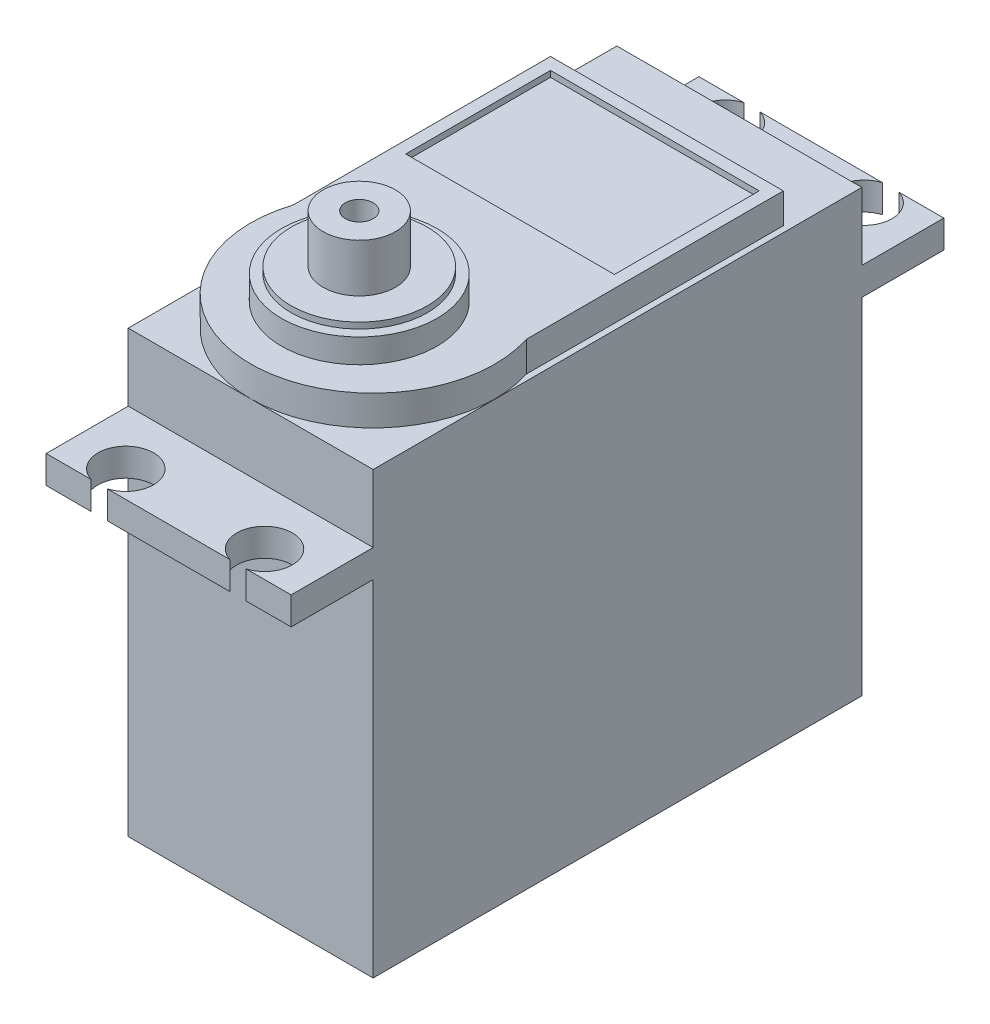
SolidWorks part; units mm, degrees
ref_plane "Front Plane" through (0, 0, 0) normal (0, 0, 1) x (1, 0, 0)
ref_plane "Top Plane" through (0, 0, 0) normal (0, 1, 0) x (1, 0, 0)
ref_plane "Right Plane" through (0, 0, 0) normal (1, 0, 0) x (0, 0, -1)
sketch "Sketch1" plane through (0, 0, 0) normal (0, 1, 0) x (1, 0, 0)
  line L1 (-10.15, -20.25) -> (10.15, -20.25)
  line L2 (-10.15, -20.25) -> (-10.15, 20.25)
  line L3 (-10.15, 20.25) -> (10.15, 20.25)
  line L4 (10.15, -20.25) -> (10.15, 20.25)
  line L5 (-10.15, -20.25) -> (10.15, 20.25) construction
  line L6 (-10.15, 20.25) -> (10.15, -20.25) construction
  point P0 (0, 0)
  dimension "D1" = 40.5
  dimension "D2" = 20.3
extrude "Boss-Extrude1" add sketch "Sketch1" along normal blind 36.5
sketch "Sketch4" plane through (0, 0, 20.25) normal (0, 0, 1) x (1, 0, 0)
  line L0 (10.15, 0) -> (10.15, 28.6) construction
  line L1 (10.15, 36.5) -> (10.15, 0) construction
  line L2 (10.15, 28.6) -> (-10.15, 28.6)
  line L3 (-10.15, 36.5) -> (-10.15, 0) construction
  line L4 (-10.15, 28.6) -> (-10.15, 30.9)
  line L5 (-10.15, 30.9) -> (10.15, 30.9)
  line L6 (10.15, 30.9) -> (10.15, 28.6)
  dimension "D1" = 28.6
  dimension "D2" = 2.3
extrude "Boss-Extrude4" add sketch "Sketch4" along normal blind 6.8 contours L5 L6 L2 L4
sketch "Sketch5" plane through (0, 30.9, 0) normal (0, 1, 0) x (1, 0, 0)
  line L0 (0, -20.25) -> (0, -22.35) construction
  line L1 (-10.15, -20.25) -> (10.15, -20.25) construction
  line L2 (-10.15, -22.35) -> (10.15, -22.35) construction
  line L3 (10.15, -27.05) -> (10.15, -20.25) construction
  line L4 (0, -22.35) -> (0, -27.05) construction
  line L5 (-10.15, -27.05) -> (10.15, -27.05) construction
  line L7 (10.15, -27.05) -> (8.05, -27.05) construction
  line L8 (8.05, -27.05) -> (5.75, -27.05)
  line L9 (5.75, -27.05) -> (5.75, -24.85)
  circle A0 centre (5.75, -24.85) radius 2.3
  circle A1 centre (-5.75, -24.85) radius 2.3
  point P10 (0, -22.35)
  line M10 (-10.15, -27.05) -> (10.15, -27.05)
  dimension "D2" = 4.6
  dimension "D1" = 2.1
  dimension "D3" = 2.1
  dimension "D4" = 2.2
  dimension "D5" = 2.3
extrude "Cut-Extrude1" cut sketch "Sketch5" against normal up to body separate body contours A1 M10 | A0 M10 region at (-5.75, 30.9, 24.8378) region at (5.75, 30.9, 24.8378)
sketch "Sketch6" plane through (-10.15, 0, 0) normal (-1, 0, 0) x (0, 0, 1)
  line L0 (0, 0) -> (0, 36.5) construction
  line L1 (-20.25, 0) -> (20.25, 0) construction
  line L2 (-20.25, 36.5) -> (20.25, 36.5) construction
ref_plane "Plane1" through (0, 0, 0) normal (0, 0, 1) x (0, 1, 0)
mirror "Mirror2" about plane through (0, 0, 0) normal (0, 0, 1) of "Cut-Extrude1", "Boss-Extrude4"
sketch "Sketch7" plane through (0, 36.5, 0) normal (0, 1, 0) x (1, 0, 0)
  line L0 (10.15, 20.25) -> (-10.15, 20.25) construction
  line L1 (10.15, -20.25) -> (10.15, 20.25) construction
  line L2 (10.15, 14.75) -> (-10.15, 14.75)
  line L3 (-10.15, 20.25) -> (-10.15, -20.25) construction
  line L4 (-10.15, 14.75) -> (-10.15, -7.05)
  line L5 (10.15, 14.75) -> (10.15, -7.05) construction
  line L6 (0, -20.25) -> (0, 11.25) construction
  line L7 (-10.15, -20.25) -> (10.15, -20.25) construction
  line L8 (-9.65, 14.25) -> (-9.65, -7.05)
  line L9 (9.65, 14.25) -> (-9.65, 14.25)
  line L10 (9.65, 14.25) -> (9.65, -7.05)
  arc A0 (9.65, -7.05) -> (-9.65, -7.05) centre (0, -10.1226) cw
  dimension "D1" = 5.5
  dimension "D2" = 13.2
  dimension "D3" = 31.5
  dimension "D4" = 0.5
extrude "Boss-Extrude5" add sketch "Sketch7" along normal blind 2.5 contours A0 L8 L9 L10
sketch "Sketch10" plane through (0, 39, 0) normal (0, 1, 0) x (1, 0, 0)
  line L0 (0, -20.25) -> (0, -11.25) construction
  arc A0 (-9.65, -7.05) -> (9.65, -7.05) centre (0, -10.1226) ccw construction
  circle A1 centre (0, -11.25) radius 6.45
  dimension "D2" = 12.9
  dimension "D1" = 9
extrude "Boss-Extrude6" add sketch "Sketch10" along normal blind 2
sketch "Sketch11" plane through (0, 41, 0) normal (0, 1, 0) x (1, 0, 0)
  circle A0 centre (0, -11.25) radius 6.45 construction
  circle A1 centre (0, -11.25) radius 5.65
  dimension "D1" = 0.8
extrude "Boss-Extrude7" add sketch "Sketch11" along normal blind 0.5
sketch "Sketch12" plane through (0, 41.5, 0) normal (0, 1, 0) x (1, 0, 0)
  circle A0 centre (0, -11.25) radius 3
  dimension "D1" = 6
extrude "Boss-Extrude8" add sketch "Sketch12" along normal blind 4
sketch "Sketch13" plane through (0, 45.5, 0) normal (0, 1, 0) x (1, 0, 0)
  circle A0 centre (0, -11.25) radius 1.15
  dimension "D1" = 2.3
extrude "Cut-Extrude2" cut sketch "Sketch13" against normal blind 4
sketch "Sketch14" plane through (0, 39, 0) normal (0, 1, 0) x (1, 0, 0)
  line L0 (9.65, 14.25) -> (-9.65, 14.25) construction
  line L1 (-8.65, 13.25) -> (8.65, 13.25)
  line L2 (-8.65, 13.25) -> (-8.65, 1.25)
  line L3 (-8.65, 1.25) -> (8.65, 1.25)
  line L4 (8.65, 13.25) -> (8.65, 1.25)
  line L5 (-9.65, 14.25) -> (-9.65, -7.05) construction
  line L6 (9.65, 14.25) -> (9.65, -7.05) construction
  dimension "D1" = 1
  dimension "D2" = 1
  dimension "D3" = 1
  dimension "D4" = 12
extrude "Cut-Extrude3" cut sketch "Sketch14" against normal blind 0.5
equation "\"SpoolCenterToMotor\" = 31.5mm"
equation "\"D3@Sketch7\"=\"SpoolCenterToMotor\""
equation "\"MotorLength\" = 40.5mm"
equation "\"D1@Sketch1\"=\"MotorLength\""
equation "\"MotorWidth\" = 20.3mm"
equation "\"D2@Sketch1\"=\"MotorWidth\""
equation "\"AttachmentHeight\"= 3mm"
equation "\"SpoolDiameter\"= 60mm"
equation "\"SpoolHeight\"= 2mm"
equation "\"SpoolRidgeHeight\"= 1mm"
equation "\"SpoolRidgeDepth\"= 2mm"
equation "\"OuterThickness\"= 3mm"
equation "\"MasterFillet\"= 3mm"
equation "\"PartSeperation\"= 6mm"
equation "\"Tolerance\"= 0.15mm"
equation "\"HeightPart\"= 100mm"
equation "\"Holes\"= 1.5mm"
equation "\"SpineHolderThickness\"= 3mm"
equation "\"SpineHolderDepth\" = 3mm"
equation "\"MotorTransmitterToScrew\"= 21.7mm"
equation "\"SpoolSeperation\"= 2mm"
equation "\"ServoHolderWidthOffset\"= 20mm"
equation "\"DiscThickness\"= 4mm"
equation "\"LigamentThickness\"= 2mm"
equation "\"LigamentExtension\"= 1mm"
equation "\"LigamentAngle\"= 20deg"
equation "\"SpineDiameter\"= 15mm"
equation "\"LigamentDepth\"= 1mm"
equation "\"SpoolToSpine\"= 15mm"
equation "\"HubOffset\"= 18mm"
equation "\"ServoFastenerHolders\"=2mm"
equation "\"ArduinoLength\" = 53.4mm"
equation "\"ArduinoWidth\" = 50mm"
equation "\"ArdYOffset\" = 29.5mm"
equation "\"ArdXOffset\" = 20.5mm"
equation "\"ArdXOffsetSmall\" = 25mm"
equation "\"MiddleServoOffset\"= 12mm"
equation "\"LargeServoOffset\"= 3mm"
equation "\"SmallServoOffset\"= 0mm"
equation "\"ToolHoleDiameter\"= 12mm"
